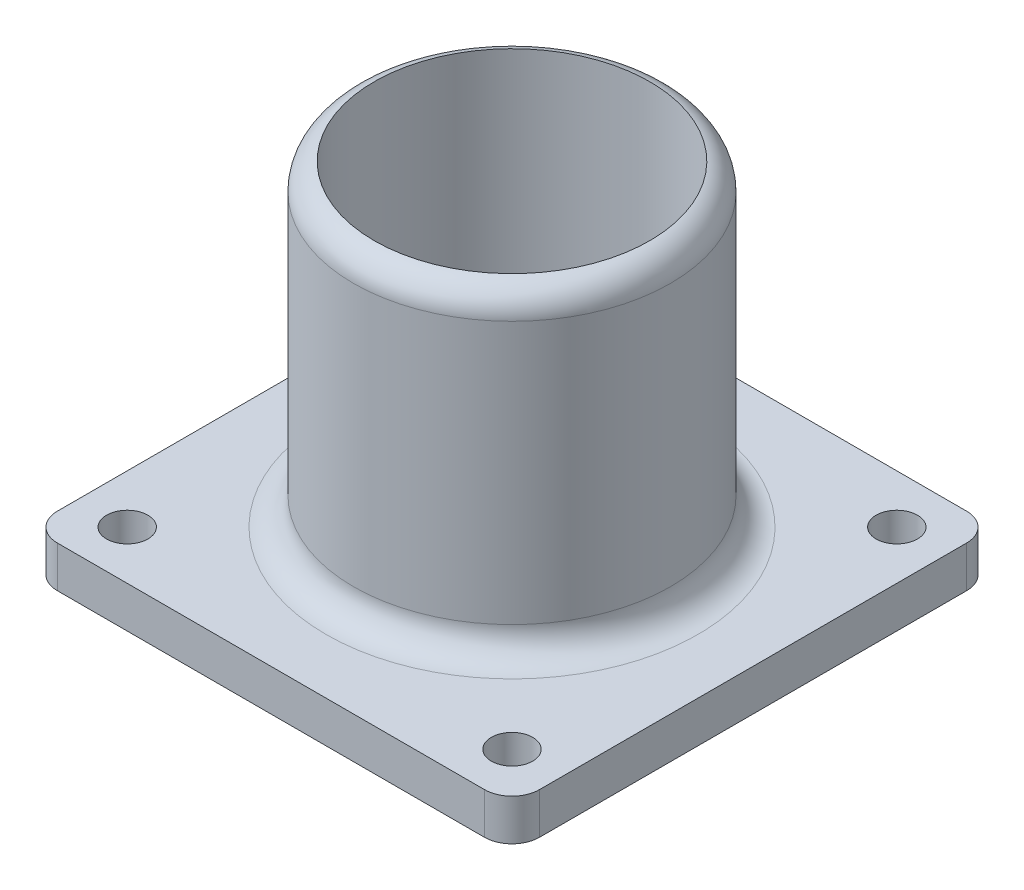
SolidWorks part; units mm, degrees
ref_plane "Plano frontal" through (0, 0, 0) normal (0, 0, 1) x (1, 0, 0)
ref_plane "Plano superior" through (0, 0, 0) normal (0, 1, 0) x (1, 0, 0)
ref_plane "Plano direito" through (0, 0, 0) normal (1, 0, 0) x (0, 0, -1)
sketch "Esboço1" plane through (0, 0, 0) normal (0, 1, 0) x (1, 0, 0)
  line L1 (-17.5, -17.5) -> (17.5, -17.5)
  line L2 (-17.5, -17.5) -> (-17.5, 17.5)
  line L3 (-17.5, 17.5) -> (17.5, 17.5)
  line L4 (17.5, -17.5) -> (17.5, 17.5)
  line L5 (-17.5, -17.5) -> (17.5, 17.5) construction
  line L6 (-17.5, 17.5) -> (17.5, -17.5) construction
  circle A0 centre (0, 0) radius 10
  circle A1 centre (-13.9645, 13.9645) radius 1.5
  circle A2 centre (13.9645, 13.9645) radius 1.5
  circle A3 centre (13.9645, -13.9645) radius 1.5
  circle A4 centre (-13.9645, -13.9645) radius 1.5
  point P0 (0, 0)
  point P13 (0, 0)
  point P16 (0, 0)
  point P19 (0, 0)
  point P22 (0, 0)
  dimension "D2" = 20
  dimension "D3" = 3
  dimension "D1" = 35
  dimension "D4" = 5
  dimension "D5" = 4
extrude "Ressalto-extrusão1" add sketch "Esboço1" along normal mid plane 3
fillet "Filete1" radius 2 4 edges at (-17.5, 0, -17.5) (17.5, 0, -17.5) (17.5, 0, 17.5) (-17.5, 0, 17.5)
sketch "Esboço2" plane through (0, 1.5, 0) normal (0, 1, 0) x (1, 0, 0)
  circle A0 centre (0, 0) radius 10
  circle A1 centre (0, 0) radius 11.5
  dimension "D1" = 20
  dimension "D2" = 1.5
extrude "Ressalto-extrusão2" add sketch "Esboço2" along normal blind 23
fillet "Filete2" radius 2 2 edges at (0, 1.5, -11.5) (0, 24.5, 11.5)
move or copy body "Corpo-Converter em corpo de malha1" [suppressed] bodies to move or copy 102 copy no translate (0, 0, 0) parameters "D1"=0, "D2"=0, "D3"=0
